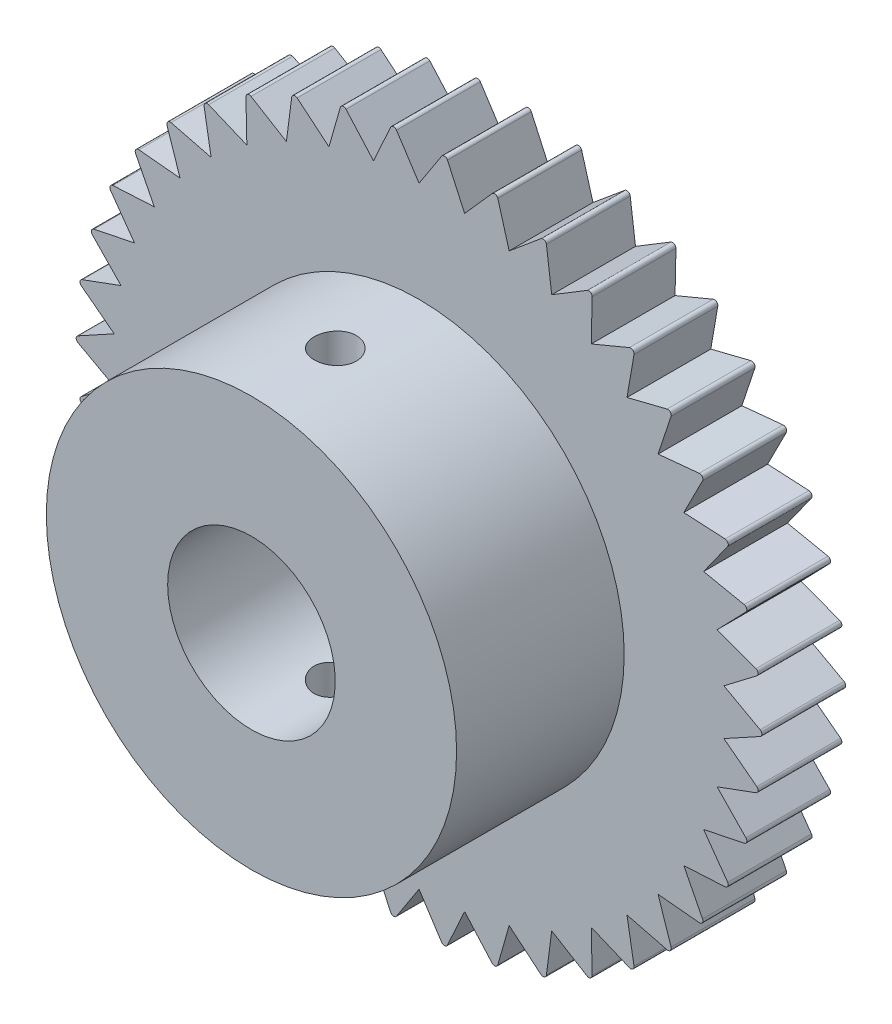
SolidWorks part; units mm, degrees
ref_plane "Front Plane" through (0, 0, 0) normal (0, 0, 1) x (1, 0, 0)
ref_plane "Top Plane" through (0, 0, 0) normal (0, 1, 0) x (1, 0, 0)
ref_plane "Right Plane" through (0, 0, 0) normal (1, 0, 0) x (0, 0, -1)
sketch "Sketch2" plane through (0, 0, 0) normal (1, 0, 0) x (0, 0, -1)
  line L0 (0, 3.175) -> (0, 13.1826)
  line L1 (0, 13.1826) -> (-3.175, 13.1826)
  line L2 (-3.175, 13.1826) -> (-3.175, 7.7724)
  line L3 (-3.175, 7.7724) -> (-9.525, 7.7724)
  line L4 (-9.525, 7.7724) -> (-9.525, 3.175)
  line L5 (-9.525, 3.175) -> (0, 3.175)
  line L6 (6.7854, 0) -> (-20.99, 0) construction
  dimension "D1" = 3.175
  dimension "D2" = 3.175
  dimension "D3" = 9.525
  dimension "D4" = 7.7724
  dimension "D5" = 13.1826
revolve "Revolve1" add sketch "Sketch2" angle 360 about L6
sketch "Sketch3" plane through (0, 0, 3.175) normal (0, 0, 1) x (1, 0, 0)
  line L1 (1.7263, 11.453) -> (0.9543, 13.148)
  line L2 (0, 11.5824) -> (1.016, 13.1434)
  line L3 (0, 11.5824) -> (-1.016, 13.1434)
  line L4 (1.7263, 11.453) -> (2.9636, 12.8452)
  line L5 (3.414, 11.0678) -> (2.9032, 12.8589)
  line L6 (3.414, 11.0678) -> (4.8449, 12.26)
  line L7 (5.0254, 10.4354) -> (4.7873, 12.2826)
  line L8 (5.0254, 10.4354) -> (6.6181, 11.401)
  line L9 (6.5246, 9.5698) -> (6.5645, 11.4319)
  line L10 (6.5246, 9.5698) -> (8.2434, 10.2872)
  line L11 (7.878, 8.4905) -> (8.195, 10.3258)
  line L12 (7.878, 8.4905) -> (9.6846, 8.9437)
  line L13 (9.0555, 7.2215) -> (9.6425, 8.9891)
  line L14 (9.0555, 7.2215) -> (10.9094, 7.4004)
  line L15 (10.0307, 5.7912) -> (10.8745, 7.4516)
  line L16 (10.0307, 5.7912) -> (11.8905, 5.6918)
  line L17 (10.7818, 4.2315) -> (11.8636, 5.7476)
  line L18 (10.7818, 4.2315) -> (12.606, 3.8561)
  line L19 (11.292, 2.5773) -> (12.5878, 3.9152)
  line L20 (11.292, 2.5773) -> (13.0399, 1.9342)
  line L21 (11.55, 0.8656) -> (13.0307, 1.9954)
  line L22 (11.55, 0.8656) -> (13.1826, -0.031)
  line L23 (11.55, -0.8656) -> (13.1826, 0.031)
  line L24 (11.55, -0.8656) -> (13.0307, -1.9954)
  line L25 (11.292, -2.5773) -> (13.0399, -1.9342)
  line L26 (11.292, -2.5773) -> (12.5878, -3.9152)
  line L27 (10.7818, -4.2315) -> (12.606, -3.8561)
  line L28 (10.7818, -4.2315) -> (11.8636, -5.7476)
  line L29 (10.0307, -5.7912) -> (11.8905, -5.6918)
  line L30 (10.0307, -5.7912) -> (10.8745, -7.4516)
  line L31 (9.0555, -7.2215) -> (10.9094, -7.4004)
  line L32 (9.0555, -7.2215) -> (9.6425, -8.9891)
  line L33 (7.878, -8.4905) -> (9.6846, -8.9437)
  line L34 (7.878, -8.4905) -> (8.195, -10.3258)
  line L35 (6.5246, -9.5698) -> (8.2434, -10.2872)
  line L36 (6.5246, -9.5698) -> (6.5645, -11.4319)
  line L37 (5.0254, -10.4354) -> (6.6181, -11.401)
  line L38 (5.0254, -10.4354) -> (4.7873, -12.2826)
  line L39 (3.414, -11.0678) -> (4.8449, -12.26)
  line L40 (3.414, -11.0678) -> (2.9032, -12.8589)
  line L41 (1.7263, -11.453) -> (2.9636, -12.8452)
  line L42 (1.7263, -11.453) -> (0.9543, -13.148)
  line L43 (0, -11.5824) -> (1.016, -13.1434)
  line L44 (0, -11.5824) -> (-1.016, -13.1434)
  line L45 (-1.7263, -11.453) -> (-0.9543, -13.148)
  line L46 (-1.7263, -11.453) -> (-2.9636, -12.8452)
  line L47 (-3.414, -11.0678) -> (-2.9032, -12.8589)
  line L48 (-3.414, -11.0678) -> (-4.8449, -12.26)
  line L49 (-5.0254, -10.4354) -> (-4.7873, -12.2826)
  line L50 (-5.0254, -10.4354) -> (-6.6181, -11.401)
  line L51 (-6.5246, -9.5698) -> (-6.5645, -11.4319)
  line L52 (-6.5246, -9.5698) -> (-8.2434, -10.2872)
  line L53 (-7.878, -8.4905) -> (-8.195, -10.3258)
  line L54 (-7.878, -8.4905) -> (-9.6846, -8.9437)
  line L55 (-9.0555, -7.2215) -> (-9.6425, -8.9891)
  line L56 (-9.0555, -7.2215) -> (-10.9094, -7.4004)
  line L57 (-10.0307, -5.7912) -> (-10.8745, -7.4516)
  line L58 (-10.0307, -5.7912) -> (-11.8905, -5.6918)
  line L59 (-10.7818, -4.2315) -> (-11.8636, -5.7476)
  line L60 (-10.7818, -4.2315) -> (-12.606, -3.8561)
  line L61 (-11.292, -2.5773) -> (-12.5878, -3.9152)
  line L62 (-11.292, -2.5773) -> (-13.0399, -1.9342)
  line L63 (-11.55, -0.8656) -> (-13.0307, -1.9954)
  line L64 (-11.55, -0.8656) -> (-13.1826, 0.031)
  line L65 (-11.55, 0.8656) -> (-13.1826, -0.031)
  line L66 (-11.55, 0.8656) -> (-13.0307, 1.9954)
  line L67 (-11.292, 2.5773) -> (-13.0399, 1.9342)
  line L68 (-11.292, 2.5773) -> (-12.5878, 3.9152)
  line L69 (-10.7818, 4.2315) -> (-12.606, 3.8561)
  line L70 (-10.7818, 4.2315) -> (-11.8636, 5.7476)
  line L71 (-10.0307, 5.7912) -> (-11.8905, 5.6918)
  line L72 (-10.0307, 5.7912) -> (-10.8745, 7.4516)
  line L73 (-9.0555, 7.2215) -> (-10.9094, 7.4004)
  line L74 (-9.0555, 7.2215) -> (-9.6425, 8.9891)
  line L75 (-7.878, 8.4905) -> (-9.6846, 8.9437)
  line L76 (-7.878, 8.4905) -> (-8.195, 10.3258)
  line L77 (-6.5246, 9.5698) -> (-8.2434, 10.2872)
  line L78 (-6.5246, 9.5698) -> (-6.5645, 11.4319)
  line L79 (-5.0254, 10.4354) -> (-6.6181, 11.401)
  line L80 (-5.0254, 10.4354) -> (-4.7873, 12.2826)
  line L81 (-3.414, 11.0678) -> (-4.8449, 12.26)
  line L82 (-3.414, 11.0678) -> (-2.9032, 12.8589)
  line L83 (-1.7263, 11.453) -> (-2.9636, 12.8452)
  line L84 (-1.7263, 11.453) -> (-0.9543, 13.148)
  circle A0 centre (0, 0) radius 13.1826 construction
  circle M1 centre (0, 0) radius 7.7724
  dimension "D1" = 42
  dimension "D3" = 2.032
extrude "Cut-Extrude3" cut sketch "Sketch3" against normal through all and the other way through all flip side to cut contours L84 L83 L82 L81 L80 L79 L78 L77 L76 L75 L74 L73 L72 L71 L70 L69 L68 L67 L66 L65 L64 L63 L62 L61 L60 L59 L58 L57 L56 L55 L54 L53 L52 L51 L50 L49 L48 L47 L46 L45 L44 L43 L42 L41 L40 L39 L38 L37 L36 L35 L34 | M1 region at (2.6007, 11.8788, 3.175) region at (0, 0, 3.175)
fillet "Fillet1" radius 0.127 42 edges at (-10.8454, -7.3943, 1.5875) (-11.8263, -5.6952, 1.5875) (-12.543, -3.869, 1.5875) (-12.9796, -1.9564, 1.5875) (-13.1262, 0, 1.5875) (-12.9796, 1.9564, 1.5875) (-12.543, 3.869, 1.5875) (-11.8263, 5.6952, 1.5875) (-10.8454, 7.3943, 1.5875) (-9.6222, 8.9281, 1.5875) (-8.1841, 10.2625, 1.5875) (-6.5631, 11.3676, 1.5875) (-4.7955, 12.2188, 1.5875) (-2.9209, 12.7971, 1.5875) (-0.9809, 13.0895, 1.5875) (0.9809, 13.0895, 1.5875) (2.9209, 12.7971, 1.5875) (4.7955, 12.2188, 1.5875) (6.5631, 11.3676, 1.5875) (8.1841, 10.2625, 1.5875) (9.6222, 8.9281, 1.5875) (10.8454, 7.3943, 1.5875) (11.8263, 5.6952, 1.5875) (12.543, 3.869, 1.5875) (12.9796, 1.9564, 1.5875) (13.1262, 0, 1.5875) (12.9796, -1.9564, 1.5875) (-9.6222, -8.9281, 1.5875) (-8.1841, -10.2625, 1.5875) (-6.5631, -11.3676, 1.5875) (-4.7955, -12.2188, 1.5875) (-2.9209, -12.7971, 1.5875) (-0.9809, -13.0895, 1.5875) (0.9809, -13.0895, 1.5875) (2.9209, -12.7971, 1.5875) (4.7955, -12.2188, 1.5875) (6.5631, -11.3676, 1.5875) (8.1841, -10.2625, 1.5875) (9.6222, -8.9281, 1.5875) (10.8454, -7.3943, 1.5875) (11.8263, -5.6952, 1.5875) (12.543, -3.869, 1.5875)
sketch "Sketch4" plane through (0, 0, 0) normal (0, 1, 0) x (1, 0, 0)
  line L0 (-7.7724, -9.525) -> (7.7724, -9.525) construction
  circle A0 centre (0, -6.35) radius 0.8001
  dimension "D2" = 1.6002
  dimension "D1" = 3.175
extrude "Cut-Extrude4" cut sketch "Sketch4" against normal through all and the other way through all
